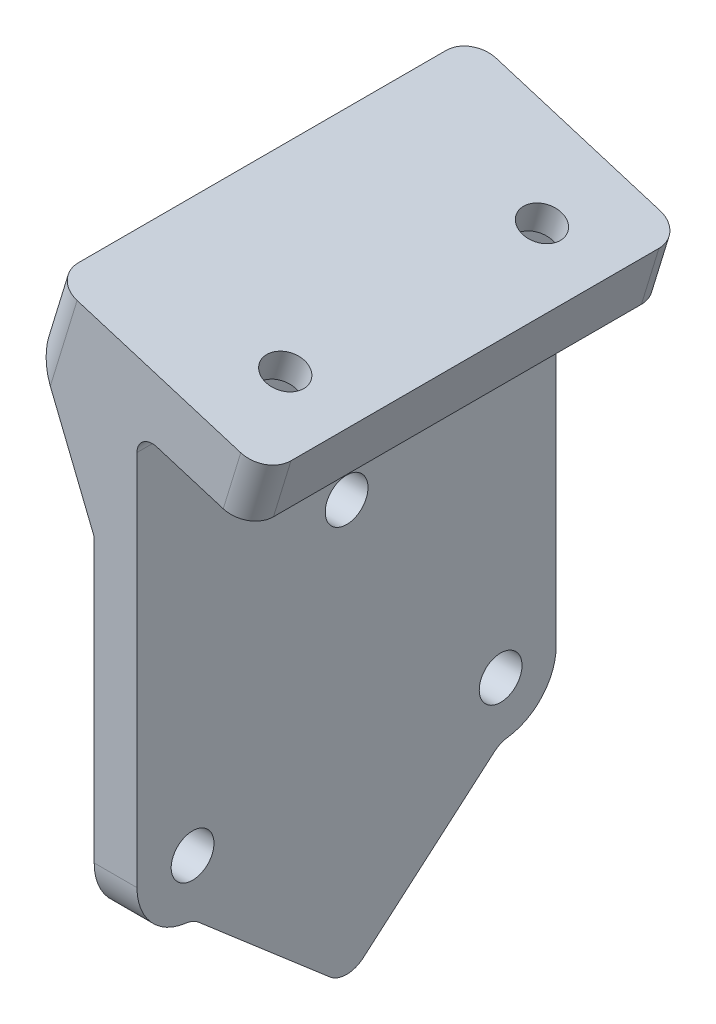
SolidWorks part; units mm, degrees
ref_plane "Plan de face" through (0, 0, 0) normal (0, 0, 1) x (1, 0, 0)
ref_plane "Plan de dessus" through (0, 0, 0) normal (0, 1, 0) x (1, 0, 0)
ref_plane "Plan de droite" through (0, 0, 0) normal (1, 0, 0) x (0, 0, -1)
sketch "Esquisse1" plane through (0, 0, 0) normal (0, 0, 1) x (1, 0, 0)
  line L0 (0, 0) -> (-24.8639, 7.6017)
  line L1 (-24.8639, 7.6017) -> (-26.9105, 0.9075)
  line L2 (-26.9105, 0.9075) -> (-20, -1.2052)
  line L3 (-20, -1.2052) -> (-20, -71.2052)
  line L4 (-20, -71.2052) -> (-15, -71.2052)
  line L5 (-15, -71.2052) -> (-15, -2.7339)
  line L6 (-15, -2.7339) -> (-2.0466, -6.6941)
  line L7 (-2.0466, -6.6941) -> (0, 0)
  line L8 (-24.8639, 7.6017) -> (-0.4628, 7.6017) construction
  dimension "D1" = 7
  dimension "D2" = 26
  dimension "D3" = 17
  dimension "D4" = 15
  dimension "D5" = 5
  dimension "D6" = 70
extrude "Boss.-Extru.1" add sketch "Esquisse1" along normal blind 49
sketch "Esquisse2" plane through (0, 0, 0) normal (0.2924, 0.9563, 0) x (0.9563, -0.2924, 0)
  line L0 (-7.5, 0) -> (-7.5, -49) construction
  line L1 (0, 0) -> (-26, 0) construction
  line L2 (0, -49) -> (-26, -49) construction
  line L3 (0, -49) -> (0, 0) construction
  line L4 (-7.5, -24.5) -> (-17.5689, -24.5) construction
  circle A0 centre (-7.5, -9.5) radius 2.25
  circle A1 centre (-7.5, -39.5) radius 2.25
  dimension "D2" = 4.5
  dimension "D3" = 30
  dimension "D1" = 7.5
extrude "Enlèv. mat.-Extru.1" cut sketch "Esquisse2" against normal up to next and the other way through all
sketch "Esquisse3" plane through (-15, 0, 0) normal (1, 0, 0) x (0, 0, -1)
  line L0 (0, -49.2052) -> (-49, -49.2052) construction
  line L1 (0, -71.2052) -> (0, -2.7339) construction
  line L2 (-49, -71.2052) -> (-49, -2.7339) construction
  line L3 (-49, -71.2052) -> (0, -71.2052) construction
  line L4 (-24.5, -49.2052) -> (-24.5, -22.2052) construction
  circle A0 centre (-42.5, -49.2052) radius 2.5
  circle A1 centre (-6.5, -49.2052) radius 2.5
  circle A2 centre (-24.5, -22.2052) radius 2.5
  dimension "D2" = 5
  dimension "D3" = 36
  dimension "D4" = 27
  dimension "D1" = 22
extrude "Enlèv. mat.-Extru.2" cut sketch "Esquisse3" against normal up to next
sketch "Esquisse4" plane through (-15, 0, 0) normal (1, 0, 0) x (0, 0, -1)
  line L0 (-42.5, -49.2052) -> (-49, -49.2052) construction
  line L3 (-24.5, -71.2052) -> (-42.5, -55.7052)
  line L5 (-49, -71.2052) -> (0, -71.2052) construction
  line L6 (-42.5, -55.7052) -> (-42.5, -49.2052) construction
  line L7 (-24.5, -71.2052) -> (-24.5, -37.1138) construction
  line L8 (-6.5, -55.7052) -> (-6.5, -49.2052) construction
  line L9 (-6.5, -49.2052) -> (0, -49.2052) construction
  line L10 (-24.5, -71.2052) -> (-6.5, -55.7052)
  line L11 (-49, -49.2052) -> (-50, -49.2052)
  line L12 (-50, -49.2052) -> (-50, -72.2052)
  line L13 (-50, -72.2052) -> (1, -72.2052)
  line L14 (1, -72.2052) -> (1, -49.2052)
  line L15 (1, -49.2052) -> (0, -49.2052)
  arc A0 (-49, -49.2052) -> (-42.5, -55.7052) centre (-42.5, -49.2052) ccw
  arc A1 (0, -49.2052) -> (-6.5, -55.7052) centre (-6.5, -49.2052) cw
  dimension "D1" = 6.5
  dimension "D2" = 1
  dimension "D3" = 1
extrude "Enlèv. mat.-Extru.3" cut sketch "Esquisse4" against normal up to next (5 mm away)
fillet "Congé1" radius 3 1 edges at (-17.5, -71.2052, 24.5)
sketch "Esquisse5" plane through (0, 0, 0) normal (0.2924, 0.9563, 0) x (0.9563, -0.2924, 0)
  line L0 (0, -24.5) -> (-19.2375, -24.5) construction
  line L1 (-3.95, -11.5496) -> (-3.95, -7.4504)
  line L2 (-3.95, -7.4504) -> (-7.5, -5.4008)
  line L3 (-7.5, -5.4008) -> (-11.05, -7.4504)
  line L4 (-11.05, -7.4504) -> (-11.05, -11.5496)
  line L5 (-11.05, -11.5496) -> (-7.5, -13.5992)
  line L6 (-7.5, -13.5992) -> (-3.95, -11.5496)
  line L7 (0, -49) -> (0, 0) construction
  line L8 (-7.5, -35.4008) -> (-3.95, -37.4504)
  line L9 (-11.05, -37.4504) -> (-7.5, -35.4008)
  line L10 (-11.05, -41.5496) -> (-11.05, -37.4504)
  line L11 (-7.5, -43.5992) -> (-11.05, -41.5496)
  line L12 (-3.95, -41.5496) -> (-7.5, -43.5992)
  line L13 (-3.95, -37.4504) -> (-3.95, -41.5496)
  circle A0 centre (-7.5, -9.5) radius 3.55 construction
  circle A1 centre (-7.5, -39.5) radius 3.55 construction
  dimension "D1" = 7.1
extrude "Enlèv. mat.-Extru.4" cut sketch "Esquisse5" along normal blind 3.5 from vertex starting at point (-2.0466, -6.6941, 0)
sketch "Esquisse6" plane through (0, 0, 49) normal (0, 0, 1) x (1, 0, 0)
  line L0 (-26.9105, 0.9075) -> (-20, -16.2052)
  line L1 (-20, -1.2052) -> (-20, -49.2052) construction
  line L2 (-20, -16.2052) -> (-20, -1.2052)
  line L3 (-20, -1.2052) -> (-26.9105, 0.9075)
  dimension "D1" = 15
extrude "Boss.-Extru.2" add sketch "Esquisse6" against normal up to vertex (49 mm away) up to point (-26.9105, 0.9075, 0)
fillet "Congé2" radius 1.8 1 edges at (-15, -2.7339, 24.5)
fillet "Congé3" radius 3 6 edges at (-25.8872, 4.2546, 0) (-1.0233, -3.3471, 0) (-1.0233, -3.3471, 49) (-25.8872, 4.2546, 49) (-17.5, -55.7052, 6.5) (-17.5, -55.7052, 42.5)
